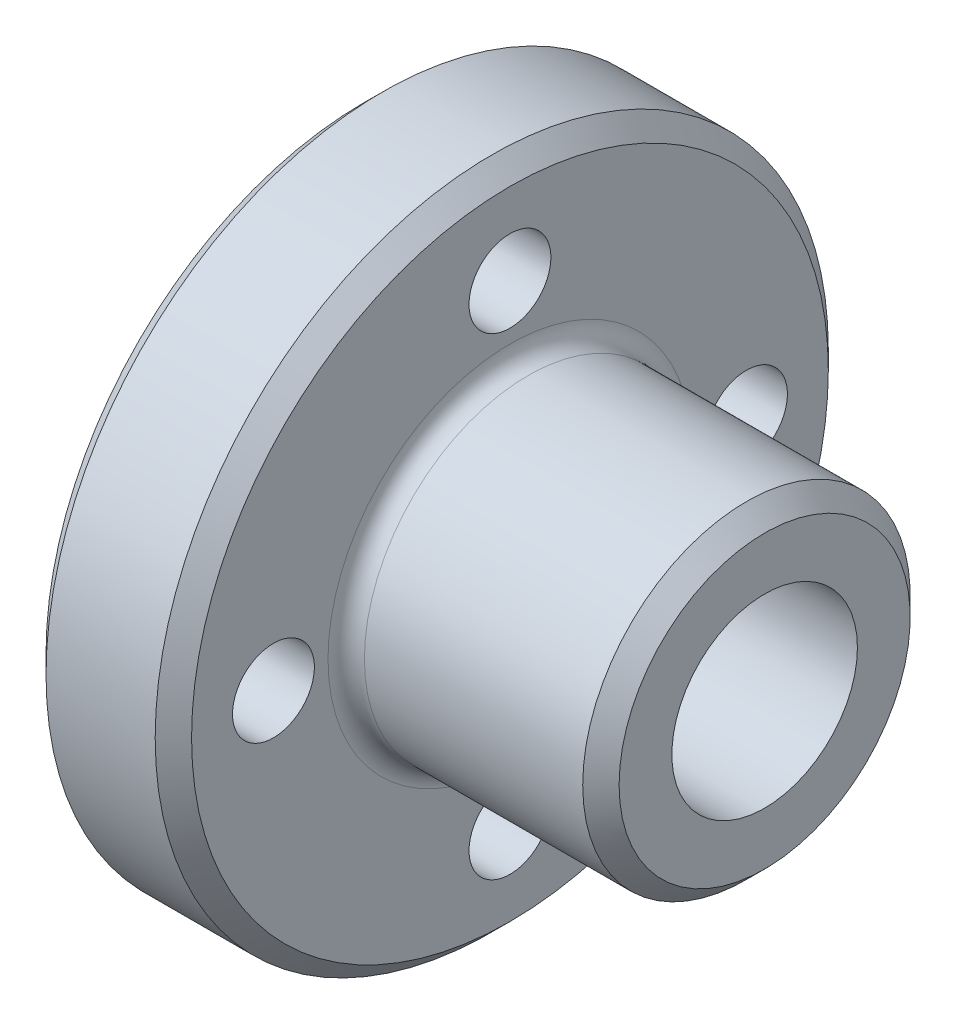
SolidWorks part; units mm, degrees
material "Ottone"
ref_plane "Piano frontale" through (0, 0, 0) normal (0, 0, 1) x (1, 0, 0)
ref_plane "Piano superiore" through (0, 0, 0) normal (0, 1, 0) x (1, 0, 0)
ref_plane "Piano destro" through (0, 0, 0) normal (1, 0, 0) x (0, 0, -1)
ref_plane "Piano1" through (0, 0, 0) normal (0, 0, 1) x (1, 0, 0)
sketch "Schizzo1" plane through (0, 0, 0) normal (0, 0, 1) x (1, 0, 0)
  line L0 (0, 0) -> (0, 18.5)
  line L2 (0, 18.5) -> (8, 18.5)
  line L4 (8, 18.5) -> (8, 9)
  line L5 (8, 9) -> (22, 9)
  line L7 (22, 9) -> (22, 0)
  line L8 (22, 0) -> (0, 0)
  line L9 (22, 0) -> (0, 0) construction
  line L10 (32.8113, 0) -> (-5.9896, 0) construction
  dimension "D1" = 37
  dimension "D2" = 18
  dimension "D3" = 8
  dimension "D4" = 22
revolve "Rivoluzione1" add sketch "Schizzo1" angle 360 about L9 reverse direction yes
hole_wizard "Foro lamato per Vite M4 a testa cilindrica piana-1" positions "Schizzo8" profile "Schizzo7" counterbore size "M4" standard "ISO" end condition through all
sketch "Schizzo8" plane through (0, 0, 0) normal (-1, 0, 0) x (0, 0, 1)
  point P0 (0, 13)
  dimension "D1" = 13
sketch "Schizzo7" plane through (0, 13, 0) normal (0, 1, 0) x (0, 0, 1)
  line L0 (0, 0) -> (0, 22)
  line L1 (0, 22) -> (2.25, 22)
  line L3 (2.25, 22) -> (2.25, 2.6)
  line L4 (2.25, 2.6) -> (4, 2.6)
  line L5 (4, 2.6) -> (4, 0)
  line L7 (4, 0) -> (0, 0)
  line L11 (0, -6.35) -> (0, 107.95) construction
  dimension "Thru Hole Dia." = 4.5
  dimension "Thru Hole Depth" = 22
  dimension "C'Bore Dia." = 8
  dimension "C'Bore Depth" = 2.6
pattern_circular "RipetizioneCircolare1" count 4 over 360 about axis through (0, 0, 0) along (-1, 0, 0) of "Foro lamato per Vite M4 a testa cilindrica piana-1"
fillet "Raccordo1" radius 1 1 edges at (8, 0, 9)
chamfer "Smusso1" distance 1 angle 45 3 edges at (0, 0, 18.5) (8, 0, 18.5) (22, 0, 9)
hole_wizard "Foro filettato M12-1" positions "Schizzo10" profile "Schizzo9" tap size "M12" standard "ISO"
sketch "Schizzo10" plane through (22, 0, 0) normal (1, 0, 0) x (0, 0, -1)
  point P0 (0, 0)
sketch "Schizzo9" plane through (22, 0, 0) normal (0, 1, 0) x (0, 0, -1)
  line L0 (0, 0) -> (0, 35.8144)
  line L1 (0, 35.8144) -> (5.1, 32.75)
  line L2 (5.1, 32.75) -> (5.1, 0)
  line L5 (5.1, 0) -> (0, 0)
  line L10 (0, 35.8144) -> (-5.1, 32.75) construction
  line L11 (0, -6.35) -> (0, 107.95) construction
  dimension "Tap Drill Dia." = 10.2
  dimension "Tap Drill Depth" = 32.75
  dimension "Drill Angle" = 118
cosmetic thread "Filettatura del foro1" parameters "D1"=22, "D2"=12
chamfer "Smusso2" distance 1 angle 45 1 edges at (0, 0, -5.1)
